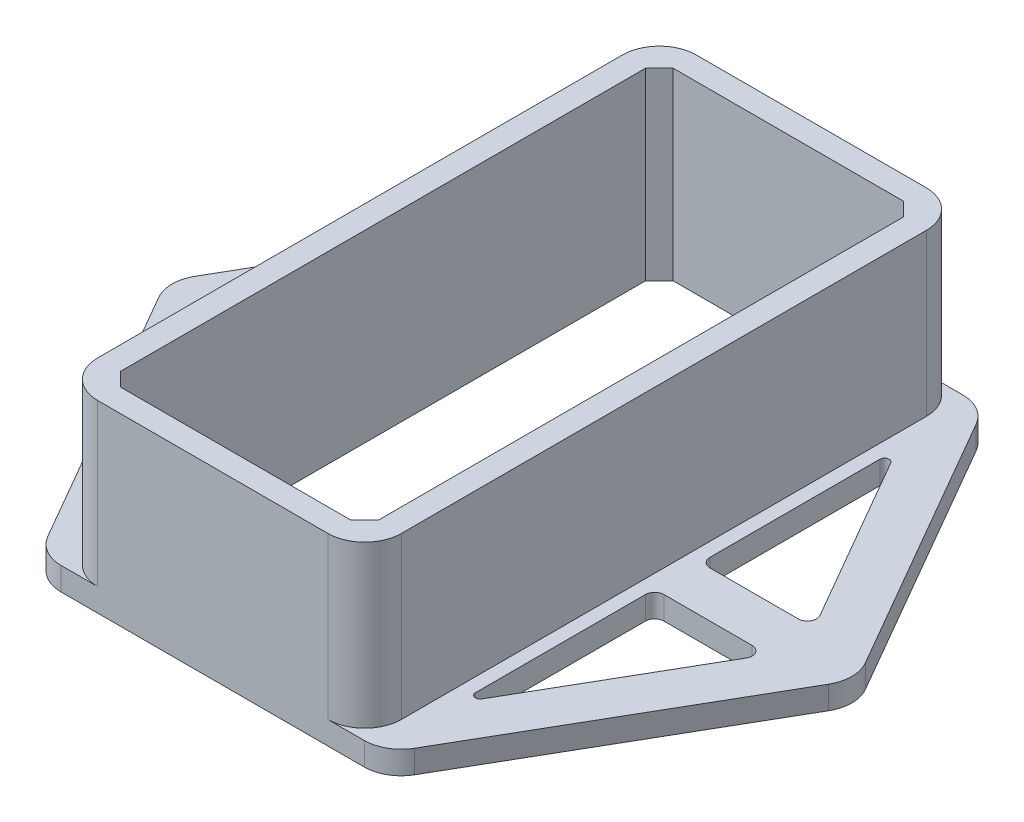
SolidWorks part; units mm, degrees
ref_plane "Front Plane" through (0, 0, 0) normal (0, 0, 1) x (1, 0, 0)
ref_plane "Top Plane" through (0, 0, 0) normal (0, 1, 0) x (1, 0, 0)
ref_plane "Right Plane" through (0, 0, 0) normal (1, 0, 0) x (0, 0, -1)
sketch "Sketch1" plane through (0, 0, 0) normal (0, 1, 0) x (1, 0, 0)
  line L1 (-75.0555, 0) -> (-37.5278, -65)
  line L2 (-37.5278, -65) -> (37.5278, -65)
  line L3 (37.5278, -65) -> (75.0555, 0)
  line L4 (75.0555, 0) -> (37.5278, 65)
  line L5 (37.5278, 65) -> (-37.5278, 65)
  line L6 (-37.5278, 65) -> (-75.0555, 0)
  circle A0 centre (0, 0) radius 65 construction
  circle A1 centre (0, 0) radius 50 construction
  dimension "D2" = 100
  dimension "D1" = 130
extrude "Boss-Extrude1" add sketch "Sketch1" along normal blind 5
fillet "Fillet1" radius 8 6 edges at (37.5278, 2.5, -65) (75.0555, 2.5, 0) (37.5278, 2.5, 65) (-37.5278, 2.5, 65) (-75.0555, 2.5, 0) (-37.5278, 2.5, -65)
sketch "Sketch3" plane through (0, 5, 0) normal (0, 1, 0) x (1, 0, 0)
  line L0 (-32.909, -65) -> (32.909, -65) construction
  line L1 (-25, 65) -> (25, 65)
  line L2 (-33, 57) -> (-33, -57)
  line L3 (-25, -65) -> (25, -65)
  line L4 (33, 57) -> (33, -57)
  line L5 (-33, 65) -> (33, -65) construction
  line L6 (-33, -65) -> (33, 65) construction
  arc A0 (33, 57) -> (25, 65) centre (25, 57) ccw
  arc A1 (33, -57) -> (25, -65) centre (25, -57) cw
  arc A2 (-25, -65) -> (-33, -57) centre (-25, -57) cw
  arc A3 (-25, 65) -> (-33, 57) centre (-25, 57) ccw
  point P0 (0, 0)
  dimension "D1" = 8
  dimension "D2" = 50
extrude "Boss-Extrude2" add sketch "Sketch3" along normal blind 35
sketch "Sketch4" plane through (0, 40, 0) normal (0, 1, 0) x (1, 0, 0)
  line L0 (-28, 57) -> (-25, 60)
  line L1 (25, 60) -> (28, 57)
  line L2 (28, -57) -> (25, -60)
  line L3 (-28, -57) -> (-25, -60)
  line L9 (-25, -60) -> (25, -60)
  line L10 (28, -57) -> (28, 57)
  line L11 (25, 60) -> (-25, 60)
  line L12 (-28, 57) -> (-28, -57)
  line L13 (-25, -60) -> (25, -60)
  line L14 (28, -57) -> (28, 57)
  line L15 (25, 60) -> (-25, 60)
  line L16 (-28, 57) -> (-28, -57)
  arc A9 (-28, -57) -> (-25, -60) centre (-25, -57) ccw
  arc A10 (25, -60) -> (28, -57) centre (25, -57) ccw
  arc A11 (28, 57) -> (25, 60) centre (25, 57) ccw
  arc A12 (-25, 60) -> (-28, 57) centre (-25, 57) ccw
  dimension "D1" = 5
extrude "Cut-Extrude1" cut sketch "Sketch4" against normal up to surface (40 mm away) up to face at (0, 0, 0)
sketch "Sketch8" plane through (0, 0, 0) normal (0, 1, 0) x (1, 0, 0)
  line L0 (0, 40) -> (0, 25) construction
  line L1 (0, 55) -> (0, 65) construction
  line L2 (9.5263, 26.5) -> (24.2487, 52) construction
  line L3 (22.5167, 55) -> (-22.5167, 55) construction
  line L4 (-24.2487, 52) -> (-9.5263, 26.5) construction
  line L5 (-12.5, 0) -> (-62.3346, 0) construction
  line L36 (6.9282, 25) -> (-6.9282, 25) construction
  line L37 (27.7128, 5) -> (57.1577, 5) construction
  line L38 (58.8897, 8) -> (36.3731, 47) construction
  line L39 (32.909, 47) -> (18.1865, 21.5) construction
  line L40 (25.1147, 6.5) -> (18.1865, 18.5) construction
  line L41 (18.1865, -21.5) -> (32.909, -47) construction
  line L42 (36.3731, -47) -> (58.8897, -8) construction
  line L43 (57.1577, -5) -> (27.7128, -5) construction
  line L44 (18.1865, -18.5) -> (25.1147, -6.5) construction
  line L45 (-9.5263, -26.5) -> (-24.2487, -52) construction
  line L46 (-22.5167, -55) -> (22.5167, -55) construction
  line L47 (24.2487, -52) -> (9.5263, -26.5) construction
  line L48 (-6.9282, -25) -> (6.9282, -25) construction
  line L49 (-27.7128, -5) -> (-57.1577, -5) construction
  line L50 (-58.8897, -8) -> (-36.3731, -47) construction
  line L51 (-32.909, -47) -> (-18.1865, -21.5) construction
  line L52 (-25.1147, -6.5) -> (-18.1865, -18.5) construction
  line L53 (-18.1865, 21.5) -> (-32.909, 47) construction
  line L54 (-37.866, 44.4141) -> (-58.8897, 8)
  line L55 (-57.1577, 5) -> (-38, 5)
  line L56 (-18.1865, 18.5) -> (-25.1147, 6.5) construction
  line L57 (-36, 7) -> (-36, 43.9141)
  line L58 (-33, 57) -> (-33, -57) construction
  line L59 (-36, -7) -> (-36, -43.9141)
  line L60 (-36.3731, 47) -> (-36, 47.6462) construction
  line L61 (-36, 5) -> (-27.7128, 5) construction
  line L71 (-33, 57) -> (-33, -57) construction
  line L72 (-57.1577, -5) -> (-38, -5)
  line L73 (-37.866, -44.4141) -> (-58.8897, -8)
  line L74 (37.866, -44.4141) -> (58.8897, -8)
  line L75 (57.1577, -5) -> (38, -5)
  line L76 (36, -7) -> (36, -43.9141)
  line L77 (36, 7) -> (36, 43.9141)
  line L78 (57.1577, 5) -> (38, 5)
  line L79 (37.866, 44.4141) -> (58.8897, 8)
  circle A0 centre (0, 0) radius 12.5 construction
  circle A1 centre (0, 40) radius 15 construction
  arc A3 (-22.5167, 55) -> (-24.2487, 52) centre (-22.5167, 53) ccw
  arc A4 (24.2487, 52) -> (22.5167, 55) centre (22.5167, 53) ccw construction
  arc A5 (6.9282, 25) -> (9.5263, 26.5) centre (6.9282, 28) ccw construction
  arc A6 (-6.9282, 25) -> (-9.5263, 26.5) centre (-6.9282, 28) cw construction
  arc A7 (25.1147, 6.5) -> (27.7128, 5) centre (27.7128, 8) ccw construction
  arc A8 (57.1577, 5) -> (58.8897, 8) centre (57.1577, 7) ccw construction
  arc A9 (36.3731, 47) -> (32.909, 47) centre (34.641, 46) ccw construction
  arc A10 (18.1865, 18.5) -> (18.1865, 21.5) centre (20.7846, 20) cw construction
  arc A11 (18.1865, -18.5) -> (18.1865, -21.5) centre (20.7846, -20) ccw construction
  arc A12 (32.909, -47) -> (36.3731, -47) centre (34.641, -46) ccw construction
  arc A13 (58.8897, -8) -> (57.1577, -5) centre (57.1577, -7) ccw construction
  arc A14 (25.1147, -6.5) -> (27.7128, -5) centre (27.7128, -8) cw construction
  arc A15 (-6.9282, -25) -> (-9.5263, -26.5) centre (-6.9282, -28) ccw construction
  arc A16 (-24.2487, -52) -> (-22.5167, -55) centre (-22.5167, -53) ccw construction
  arc A17 (22.5167, -55) -> (24.2487, -52) centre (22.5167, -53) ccw construction
  arc A18 (6.9282, -25) -> (9.5263, -26.5) centre (6.9282, -28) cw construction
  arc A19 (-25.1147, -6.5) -> (-27.7128, -5) centre (-27.7128, -8) ccw construction
  arc A20 (-57.1577, -5) -> (-58.8897, -8) centre (-57.1577, -7) ccw construction
  arc A21 (-36.3731, -47) -> (-32.909, -47) centre (-34.641, -46) ccw construction
  arc A22 (-18.1865, -18.5) -> (-18.1865, -21.5) centre (-20.7846, -20) cw construction
  arc A23 (-18.1865, 18.5) -> (-18.1865, 21.5) centre (-20.7846, 20) ccw construction
  arc A24 (-32.909, 47) -> (-36.3731, 47) centre (-34.641, 46) ccw construction
  arc A25 (-58.8897, 8) -> (-57.1577, 5) centre (-57.1577, 7) ccw
  arc A26 (-25.1147, 6.5) -> (-27.7128, 5) centre (-27.7128, 8) cw construction
  arc A28 (57.1577, -5) -> (58.8897, -8) centre (57.1577, -7) cw construction
  arc A31 (-36, 7) -> (-38, 5) centre (-38, 7) cw
  arc A32 (-36, 43.9141) -> (-37.866, 44.4141) centre (-37, 43.9141) ccw
  arc A33 (-36, -43.9141) -> (-37.866, -44.4141) centre (-37, -43.9141) cw
  arc A34 (-36, -7) -> (-38, -5) centre (-38, -7) ccw
  arc A35 (-58.8897, -8) -> (-57.1577, -5) centre (-57.1577, -7) cw
  arc A36 (57.1577, -5) -> (58.8897, -8) centre (57.1577, -7) cw construction
  arc A37 (58.8897, -8) -> (57.1577, -5) centre (57.1577, -7) ccw
  arc A38 (36, -7) -> (38, -5) centre (38, -7) cw
  arc A39 (36, -43.9141) -> (37.866, -44.4141) centre (37, -43.9141) ccw
  arc A40 (36, 43.9141) -> (37.866, 44.4141) centre (37, 43.9141) cw
  arc A41 (36, 7) -> (38, 5) centre (38, 7) ccw
  arc A42 (58.8897, 8) -> (57.1577, 5) centre (57.1577, 7) cw
  point P19 (0, 25)
  point P30 (0, 0)
  point P66 (0, 0)
  point P88 (0, 0)
  dimension "D1" = 25
  dimension "D3" = 30
  dimension "D6" = 2
  dimension "D8" = 3
  dimension "D11" = 2
  dimension "D12" = 1
  dimension "D2" = 40
  dimension "D4" = 10
  dimension "D5" = 15
  dimension "D7" = 25
  dimension "D9" = 3
extrude "Cut-Extrude2" cut sketch "Sketch8" along normal up to surface (5 mm away) contours A32 | L54 A25 L55 L57 | A35 L73 A33 L59 A34 L72 | L76 A39 L74 A37 L75 A38 | A42 L79 A40 L77 A41 L78 region at (-44.1761, 0, -19.1857) region at (-44.1761, 0, 19.1857) region at (44.1761, 0, 19.1857) region at (44.1761, 0, -19.1857) up to face at (-41.2442, 5, 0)
